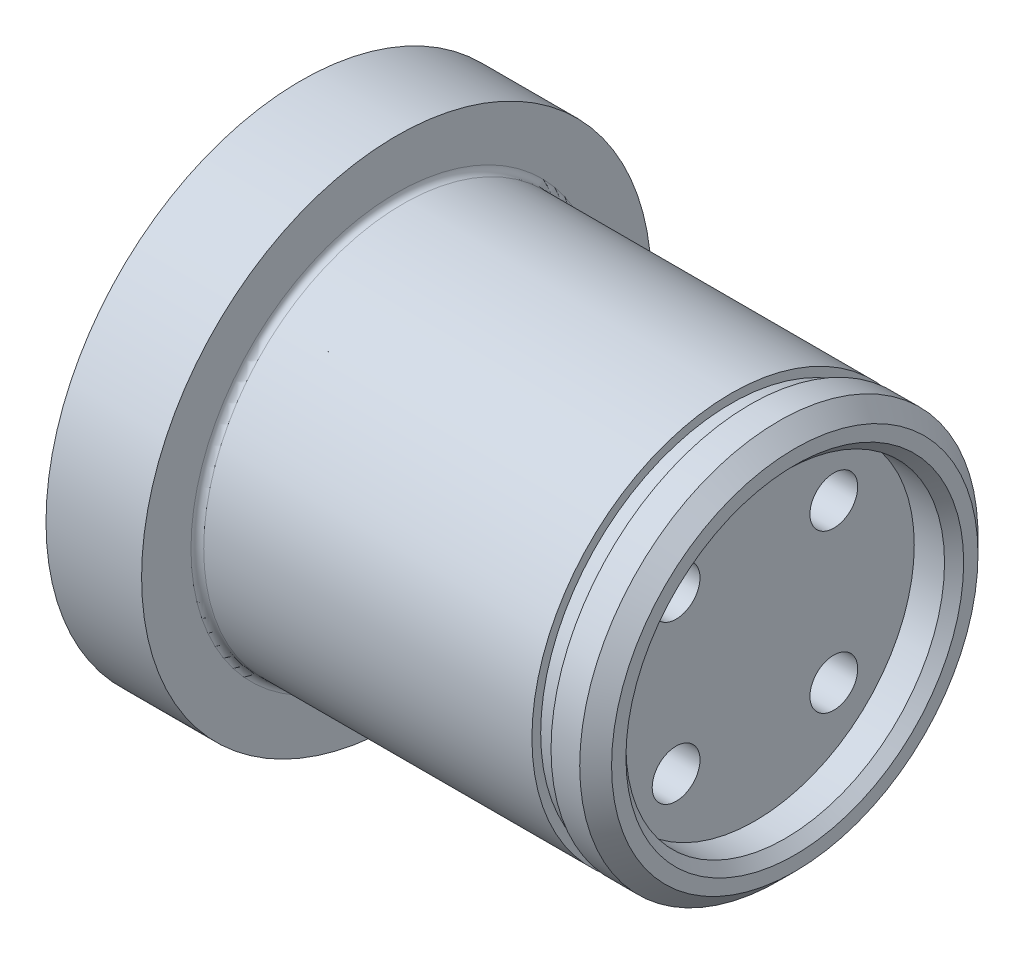
SolidWorks part; units mm, degrees
material "1060 Сплав"
ref_plane "Спереди" through (0, 0, 0) normal (0, 0, 1) x (1, 0, 0)
ref_plane "Сверху" through (0, 0, 0) normal (0, 1, 0) x (1, 0, 0)
ref_plane "Справа" through (0, 0, 0) normal (1, 0, 0) x (0, 0, -1)
sketch "Эскиз1" plane through (0, 0, 0) normal (0, 0, 1) x (1, 0, 0)
  line L0 (0, 0) -> (22138.4448, 0) construction
  line L1 (0, 0) -> (0, 12.5)
  line L2 (0, 12.5) -> (-25, 12.5)
  line L3 (-25, 12.5) -> (-25, 16)
  line L4 (-25, 16) -> (-31, 16)
  line L5 (-31, 16) -> (-31, 0)
  line L8 (0, 0) -> (-31, 0)
  dimension "D1" = 31
  dimension "D2" = 6
  dimension "D3" = 25
  dimension "D6" = 32
revolve "Повернуть1" add sketch "Эскиз1" angle 360 about L0
sketch "Эскиз2" plane through (0, 0, 0) normal (0, 0, 1) x (1, 0, 0)
  line L0 (-4, 12.5) -> (-4, 11.95)
  line L1 (0, 12.5) -> (-25, 12.5) construction
  line L2 (-4, 11.95) -> (-2.8, 11.95)
  line L3 (-2.8, 11.95) -> (-2.8, 12.5)
  line L4 (-2.8, 12.5) -> (-4, 12.5)
  line L5 (0, -12.5) -> (0, 12.5) construction
  line L6 (0, 0) -> (-50000, 0) construction
  point P10 (-2.8, 12.225)
  point P13 (0, 0)
  dimension "D1" = 4
  dimension "D2" = 1.2
  dimension "D3" = 23.9
revolve "Вырез-Повернуть1" cut sketch "Эскиз2" angle 360 about L6
chamfer "Фаска1" distance 1 angle 45 1 edges at (0, 0, 12.5)
fillet "Скругление1" radius 0.4 1 edges at (-25, 0, 12.5)
hole_wizard "Отверстие1" positions "Эскиз3" profile "Эскиз4" legacy end condition through all
sketch "Эскиз3" plane through (0, 0, 0) normal (1, 0, 0) x (0, 0, -1)
  line L0 (0, 0) -> (0, 7) construction
  line L2 (0, 0) -> (4.9497, 4.9497) construction
  circle A0 centre (0, 0) radius 7 construction
  point P0 (4.9497, 4.9497)
  dimension "D1" = 14
  dimension "D2" = 45
sketch "Эскиз4" plane through (0, 4.9497, -4.9497) normal (0, 1, 0) x (0, 0, -1)
  line L0 (0, 0) -> (0, 31)
  line L1 (0, 31) -> (1.5, 31)
  line L2 (1.5, 31) -> (1.5, 0)
  line L3 (1.5, 0) -> (0, 0)
  line L4 (0, 110) -> (0, -10) construction
  dimension "Диаметр" = 3
  dimension "Глубина" = 31
pattern_circular "Круговой массив1" count 4 over 360 about axis through (0, 0, 0) along (-1, 0, 0) of "Отверстие1"
sketch "Эскиз5" plane through (0, 0, 0) normal (0, 0, 1) x (1, 0, 0)
  line L0 (0, 0) -> (0, 10)
  line L1 (0, -11.5) -> (0, 11.5) construction
  line L7 (0, 10) -> (-2.5, 10)
  line L8 (-2.5, 10) -> (-2.5, 0)
  line L9 (-2.5, 0) -> (0, 0)
  line L10 (0, 0) -> (-50000, 0) construction
  dimension "D1" = 2.5
  dimension "D2" = 20
revolve "Вырез-Повернуть2" cut sketch "Эскиз5" angle 360 about L10
chamfer "Фаска2" distance 0.6 angle 45 1 edges at (0, 0, -10)
